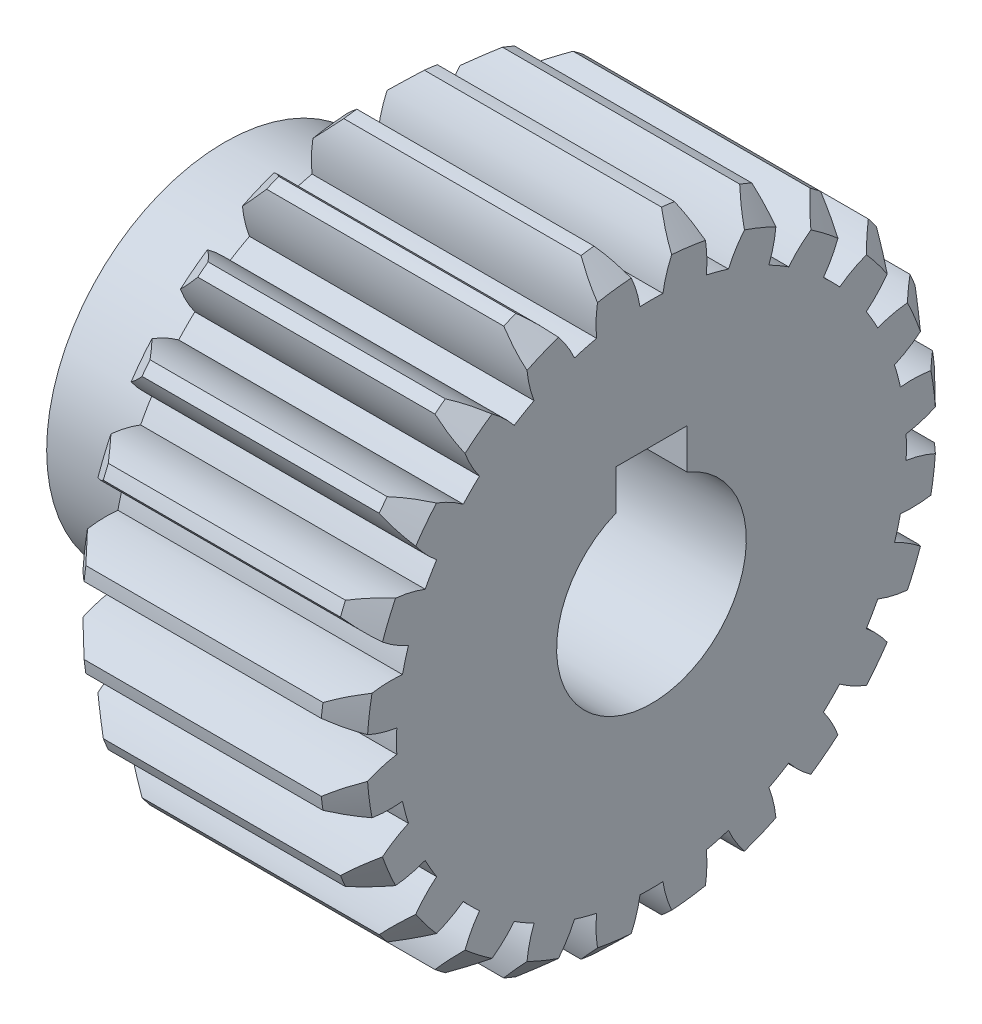
SolidWorks part; units mm, degrees
ref_plane "Plane1" through (0, 0, 0) normal (0, 0, 1) x (1, 0, 0)
ref_plane "Plane2" through (0, 0, 0) normal (0, 1, 0) x (1, 0, 0)
ref_plane "Plane3" through (0, 0, 0) normal (1, 0, 0) x (0, 0, -1)
sketch "HoldingSke" plane through (0, 0, 0) normal (0, 1, 0) x (1, 0, 0)
  line L0 (0, 0) -> (0.9135, -0.4067)
  line L1 (-15, 0) -> (100, 0) construction
  line L2 (0, 0) -> (-2.1039, 2.3779)
  line L3 (0, 0) -> (-11.863, 4.5341)
  line L4 (0, 0) -> (7.8894, 3.5126)
  line L5 (0, 0) -> (-16.8652, -6.2902)
  line L6 (0, 0) -> (-9.9476, -6.7116)
  line L7 (-2.1039, 2.3779) -> (1.771, 19.9578)
  line L8 (-76.2, 54.61) -> (-74.8, 54.61)
  line L9 (-71.009, 38.7566) -> (-53.1078, 45.2721)
  line L10 (-76.2, 71.12) -> (104.1128, 71.12)
  line L11 (0, 0) -> (-12, 0)
  line L12 (-76.2, 101.6) -> (-76.162, 101.6)
  line L13 (24.9733, 27.94) -> (52.9518, 28.4284)
  line L14 (24.9733, 27.94) -> (24.9743, 27.94)
  line L15 (24.9733, 27.94) -> (100.4006, 29.5858)
  line L16 (-63.627, -1) -> (-12.827, -1)
  circle A0 centre (0, 0) radius 4
  circle A1 centre (0, 0) radius 7.5
  circle A2 centre (0, 0) radius 7.5
  circle A3 centre (0, 0) radius 4
  dimension "MHD" = 15
  dimension "Hub_dia" = 15
  dimension "Bore" = 8
  dimension "MBD" = 8
  dimension "Num_teeth" = 24
  dimension "Pitch" = 1
  dimension "Overall_len" = 18
  dimension "Show_teeth" = 24
  dimension "Thickness" = 12
  dimension "OAL" = 18.0019
  dimension "T_dim" = 1.4
  dimension "Ap" = 20
  dimension "H" = 19.05
  dimension "Pitch_radius" = 180.3128
  dimension "Width" = 12
  dimension "Backlash" = 0.038
  dimension "Addendum_fac" = 1
  dimension "Dedendum_fac" = 1.25
  dimension "Clearance_fac" = 0.25
  dimension "Dedendum_add" = 0.001
  dimension "Module" = 1
sketch "BasProSke" plane through (0, 0, 0) normal (0, 1, 0) x (1, 0, 0)
  line L0 (-10, 0) -> (60, 0) construction
  line L1 (0, 0) -> (0, 13)
  line L2 (0, 0) -> (12, 0)
  line L3 (12, 0) -> (12, 13)
  line L4 (12, 13) -> (0, 13)
  dimension "Thickness" = 12
  dimension "Diameter" = 26
revolve "Base-Revolve" add sketch "BasProSke" angle 360 about L0
chamfer "Chamfer1" distance 1 angle 45 2 edges at (12, 0, 13) (0, 0, 13)
sketch "TooCutSke" plane through (0, 0, 0) normal (1, 0, 0) x (0, 0, -1)
  line L1 (0, 0) -> (0, 107) construction
  line L2 (0, 0) -> (-0.8513, 11.9698) construction
  line L3 (0, 0) -> (-3.127, 23.752) construction
  line L4 (-0.8513, 11.9698) -> (-1.5635, 11.876) construction
  arc A0 (0.4834, 10.7381) -> (-0.4834, 10.7381) centre (0, 0) ccw
  arc A1 (1.4409, 12.9455) -> (-1.4409, 12.9455) centre (0, 0) ccw
  circle A2 centre (0, 0) radius 12 construction
  circle A3 centre (0, 0) radius 11.2763 construction
  arc A4 (-0.4834, 10.7381) -> (-1.4409, 12.9455) centre (-5.2252, 9.9926) ccw
  arc A5 (1.4409, 12.9455) -> (0.4834, 10.7381) centre (5.2252, 9.9926) ccw
  dimension "Root_dia" = 21.498
  dimension "Overcut_dia" = 26.0508
  dimension "Pitch_dia" = 24
  dimension "Base_dia" = 22.5526
  dimension "Flank_rad" = 4.8
  dimension "Half_ang" = 7.5
  dimension "Half_CT" = 0.7183
extrude "ToothCut" cut sketch "TooCutSke" along normal through all
pattern_circular "TeethCuts" count 24 every 15 about axis through (-10, 0, 0) along (1, 0, 0) of "ToothCut"
sketch "HubNeaOneSke" plane through (0, 0, 0) normal (-1, 0, 0) x (0, 0, 1)
  circle A0 centre (0, 0) radius 7.5
  dimension "Diameter" = 15
extrude "HubNearOne" add sketch "HubNeaOneSke" along normal blind 6.0019
sketch "BorSke" plane through (0, 0, 0) normal (1, 0, 0) x (0, 0, -1)
  circle A0 centre (0, 0) radius 4
  dimension "Diameter" = 8
extrude "Bore" cut sketch "BorSke" along normal mid plane 36.0039
sketch "KeySke" plane through (0, 0, 0) normal (1, 0, 0) x (0, 0, -1)
  line L0 (-1.5, 0) -> (-1.5, 5.4)
  line L1 (-1.5, 5.4) -> (1.5, 5.4)
  line L2 (1.5, 5.4) -> (1.5, 0)
  line L3 (0, 0) -> (0, 34) construction
  line L4 (-1.5, 0) -> (1.5, 0)
  dimension "Offset" = 5.4
  dimension "Width" = 3
extrude "Keyway" cut sketch "KeySke" along normal mid plane 36.0039
sketch "Sketch2" plane through (12, 0, 0) normal (1, 0, 0) x (0, 0, -1)
  line L1 (-1.25, 5) -> (1.25, 5)
  line L2 (-1.25, 5) -> (-1.25, 15)
  line L3 (-1.25, 15) -> (1.25, 15)
  line L4 (1.25, 5) -> (1.25, 15)
  point P4 (0, 5)
  dimension "D1" = 10
  dimension "D2" = 2.5
  dimension "D3" = 5
extrude "Rotation Mark" [suppressed] cut sketch "Sketch2" against normal blind 5
equation "' \"Module@HoldingSke\" = 6.35"
equation "' \"Num_teeth@HoldingSke\" = 12"
equation "' \"Ap@HoldingSke\" =  20"
equation "' \"Ap@HoldingSke\" = 20"
equation "' \"Width@HoldingSke\" = 0.5 * 25.4"
equation "' \"Hub_dia@HoldingSke\"= 1 * 25.4"
equation "' \"Hub_dia@HoldingSke\" = 1 * 25.4"
equation "' \"Overall_len@HoldingSke\" = 1.0 * 25.4"
equation "' \"Bore@HoldingSke\" = 0.75 * 25.4"
equation "' \"T_dim@HoldingSke\" = 0.1 * 25.4"
equation "' \"Width@KeySke\" = 0.25 * 25.4"
equation "' \"Show_teeth@HoldingSke\" = 13"
equation "' \"Backlash@HoldingSke\" = 0.009 * 25.4"
equation "' \"Addendum_fac@HoldingSke\" = 1.0"
equation "' \"Dedendum_fac@HoldingSke\" = 1.25"
equation "' \"Dedendum_add@HoldingSke\" = 0.00005 * 25.4"
equation "' \"Clearance_fac@HoldingSke\" = 0.25"
equation "\"Pitch@HoldingSke\" = 1 / \"Module@HoldingSke\""
equation "\"Overcut_dia@TooCutSke\" = (\"Num_teeth@HoldingSke\" + 2 * \"Addendum_fac@HoldingSke\") / \"Pitch@HoldingSke\" + 0.002 * 25.4"
equation "\"Pitch_dia@TooCutSke\" = \"Num_teeth@HoldingSke\" / \"Pitch@HoldingSke\""
equation "\"Base_dia@TooCutSke\" = \"Num_teeth@HoldingSke\" / \"Pitch@HoldingSke\" * cos((\"Ap@HoldingSke\"  * 3.14159265 / 180))"
equation "\"Root_dia@TooCutSke\" = (\"Num_teeth@HoldingSke\" + 2) / \"Pitch@HoldingSke\" - 2 * (\"Addendum_fac@HoldingSke\" + \"Dedendum_fac@HoldingSke\") / \"Pitch@HoldingSke\" - \"Dedendum_add@HoldingSke\" * 2"
equation "\"Half_ang@TooCutSke\" = 180 / \"Num_teeth@HoldingSke\""
equation "\"Half_CT@TooCutSke\" = \"Num_teeth@HoldingSke\" / \"Pitch@HoldingSke\" * sin((3.14159265 / 2 / \"Num_teeth@HoldingSke\")) / 2 - 7 * \"Backlash@HoldingSke\" / 4"
equation "\"Flank_rad@TooCutSke\" = \"Num_teeth@HoldingSke\" / \"Pitch@HoldingSke\" / 5"
equation "\"Thickness@HoldingSke\" = \"Width@HoldingSke\""
equation "\"OAL@HoldingSke\" = \"Thickness@HoldingSke\""
equation "\"MHD@HoldingSke\" = (\"Num_teeth@HoldingSke\" + 2) / \"Pitch@HoldingSke\" - 2 * (\"Addendum_fac@HoldingSke\" + \"Dedendum_fac@HoldingSke\")  / \"Pitch@HoldingSke\" - \"Dedendum_add@HoldingSke\" * 2"
equation "\"MBD@HoldingSke\" = (\"Num_teeth@HoldingSke\" + 2) / \"Pitch@HoldingSke\" - 2 * (\"Addendum_fac@HoldingSke\" + \"Dedendum_fac@HoldingSke\")  / \"Pitch@HoldingSke\" - \"Dedendum_add@HoldingSke\" * 2 - 0.002 * 25.4"
equation "\"MHD@HoldingSke\" = ((sgn( \"MHD@HoldingSke\" - \"Hub_dia@HoldingSke\" )-1)*( \"MHD@HoldingSke\" - \"Hub_dia@HoldingSke\" ))/-2+ \"Hub_dia@HoldingSke\""
equation "\"MBD@HoldingSke\" = ((sgn( \"MBD@HoldingSke\" - \"Bore@HoldingSke\" )-1)*( \"MBD@HoldingSke\" - \"Bore@HoldingSke\" ))/-2+ \"Bore@HoldingSke\""
equation "\"OAL@HoldingSke\" = ((sgn( \"OAL@HoldingSke\" - \"Overall_len@HoldingSke\" )+1)*( \"OAL@HoldingSke\" - \"Overall_len@HoldingSke\" ))/2 + \"Overall_len@HoldingSke\" + 0.000002 * 25.4"
equation "\"Num_teeth@TeethCuts\" = int( \"Show_teeth@HoldingSke\" ) + 1"
equation "\"Num_teeth@TeethCuts\" = ((sgn( \"Num_teeth@TeethCuts\" - \"Num_teeth@HoldingSke\" )-1)*( \"Num_teeth@TeethCuts\" - \"Num_teeth@HoldingSke\" ))/-2+ \"Num_teeth@HoldingSke\""
equation "\"Num_teeth@TeethCuts\" = ((sgn( \"Num_teeth@TeethCuts\" - 2.0)+1)*( \"Num_teeth@TeethCuts\" - 2.0))/2 +2.0"
equation "\"Angle@TeethCuts\" = 360.0 / \"Num_teeth@HoldingSke\""
equation "\"Diameter@BasProSke\" = (\"Num_teeth@HoldingSke\" + 2 * \"Addendum_fac@HoldingSke\") / \"Pitch@HoldingSke\""
equation "\"Thickness@BasProSke\"  = \"Thickness@HoldingSke\""
equation "' \"Fillet_rad@BasProSke\" =  \"Thickness@HoldingSke\" * 0.05"
equation "' \"Fillet_rad@BasProSke\" = \"Thickness@HoldingSke\" * 0.05"
equation "\"MHD@HoldingSke\" = ((sgn( \"MHD@HoldingSke\" - \"Root_dia@TooCutSke\" )-1)*( \"MHD@HoldingSke\" - \"Root_dia@TooCutSke\" ))/-2+ \"Root_dia@TooCutSke\""
equation "\"Diameter@HubNeaOneSke\" = \"MHD@HoldingSke\""
equation "\"Length@HubNearOne\" = \"OAL@HoldingSke\" - \"Thickness@BasProSke\""
equation "\"Diameter@BorSke\" = \"MBD@HoldingSke\""
equation "\"D1@Bore\" = \"OAL@HoldingSke\" * 2.0"
equation "\"D1@Keyway\" = \"OAL@HoldingSke\" * 2.0"
equation "\"Offset@KeySke\" = \"T_dim@HoldingSke\" + \"MBD@HoldingSke\" / 2.0"
